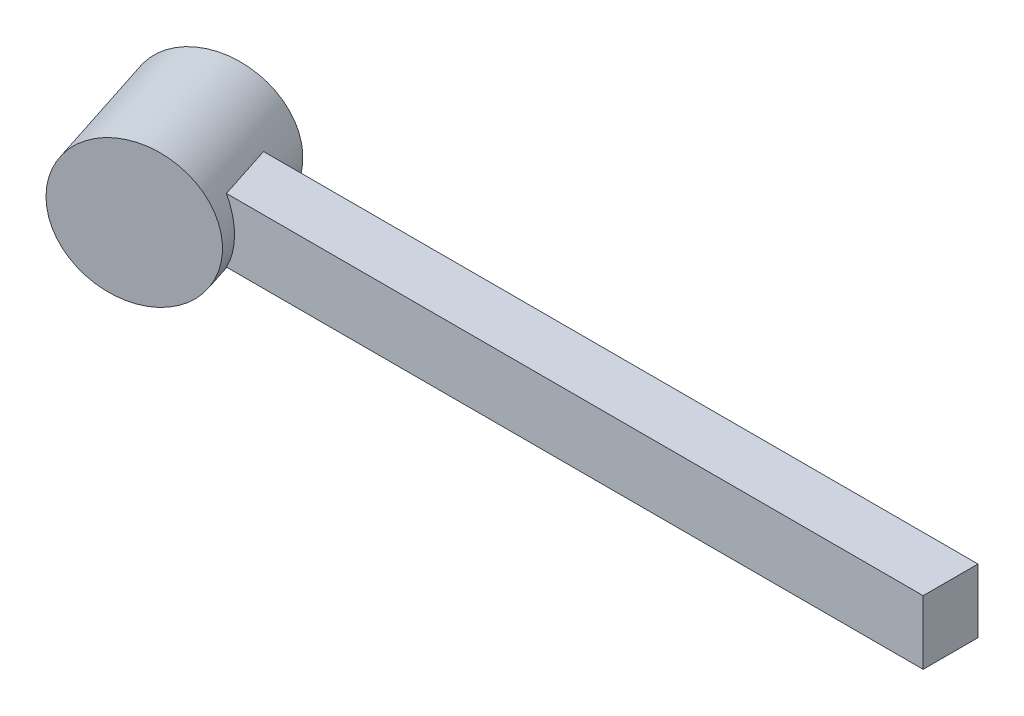
SolidWorks part; units mm, degrees
ref_plane "Front" through (0, 0, 0) normal (0, 0, 1) x (1, 0, 0)
ref_plane "Top" through (0, 0, 0) normal (0, 1, 0) x (1, 0, 0)
ref_plane "Right" through (0, 0, 0) normal (1, 0, 0) x (0, 0, -1)
sketch "Croquis1" plane through (0, 0, 0) normal (0, 1, 0) x (1, 0, 0)
  line L1 (-6.7969, 1.7187) -> (18.2031, 1.7187)
  line L2 (-6.7969, 1.7187) -> (-6.7969, 0)
  line L3 (-6.7969, 0) -> (18.2031, 0)
  line L4 (18.2031, 1.7187) -> (18.2031, 0)
  dimension "D1" = 25
extrude "Saliente-Extruir1" add sketch "Croquis1" along normal blind 1 and the other way blind 1
sketch "Croquis2" plane through (0, 0, 0) normal (0, 1, 0) x (1, 0, 0)
  line L0 (-6.6159, 2.8731) -> (-5.1617, -1.616) construction
  line L1 (-6.4926, 2.4927) -> (-8.5817, 1.816)
  line L2 (-8.5817, 1.816) -> (-7.3747, -1.9099)
  line L3 (-7.3747, -1.9099) -> (-5.2857, -1.2332)
  line L4 (-6.4926, 2.4927) -> (-5.2857, -1.2332)
revolve "Revolución1" add sketch "Croquis2" angle 360 about L0
